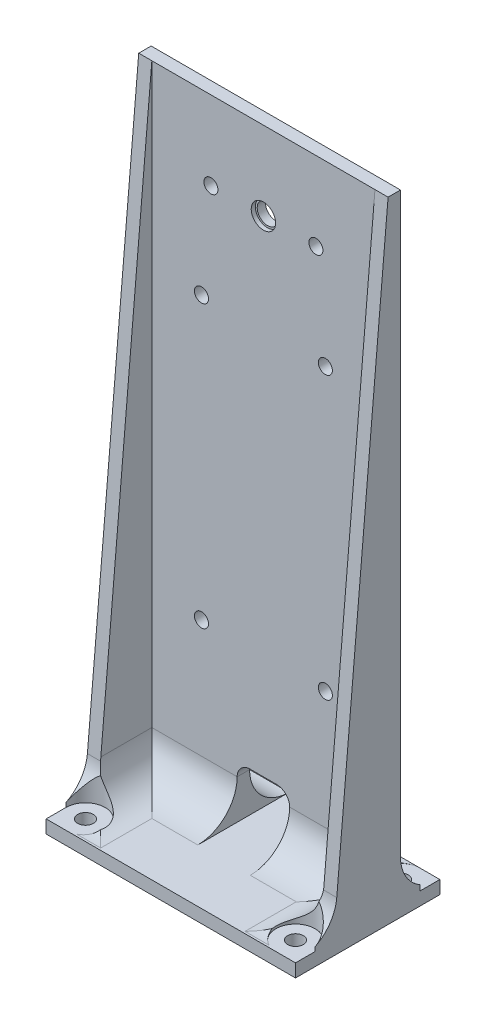
SolidWorks part; units mm, degrees
ref_plane "Front Plane" through (0, 0, 0) normal (0, 0, 1) x (1, 0, 0)
ref_plane "Top Plane" through (0, 0, 0) normal (0, 1, 0) x (1, 0, 0)
ref_plane "Right Plane" through (0, 0, 0) normal (1, 0, 0) x (0, 0, -1)
sketch "Sketch1" plane through (0, 0, 0) normal (0, 1, 0) x (1, 0, 0)
  line L0 (-30.1625, 17.4625) -> (30.1625, 17.4625)
  line L1 (-25.4, -12.7) -> (25.4, -12.7)
  line L2 (-25.4, -12.7) -> (-25.4, 12.7)
  line L3 (-25.4, 12.7) -> (25.4, 12.7)
  line L4 (25.4, -12.7) -> (25.4, 12.7)
  line L5 (-25.4, -12.7) -> (25.4, 12.7) construction
  line L6 (-25.4, 12.7) -> (25.4, -12.7) construction
  line L7 (30.1625, -17.4625) -> (30.1625, 17.4625)
  line L8 (-30.1625, -17.4625) -> (30.1625, -17.4625)
  line L9 (-30.1625, -17.4625) -> (-30.1625, 17.4625)
  point P0 (0, 0)
  dimension "D1" = 50.8
  dimension "D2" = 25.4
  dimension "D3" = 4.7625
extrude "Boss-Extrude1" add sketch "Sketch1" along normal blind 3.175 contours L1 L4 L3 L2 | L9 L8 L7 L0 L4 L1 L2 L3 region at (0, 0, -16.7654) region at (0, 0, 0)
hole_wizard "#6 Clearance Hole1" positions "Sketch2" profile "Sketch3" hole size "#6" standard "ANSI Inch"
sketch "Sketch2" plane through (0, 0, 0) normal (0, -1, 0) x (-1, 0, 0)
  point P0 (25.4, -12.7)
  point P3 (25.4, 12.7)
  point P6 (-25.4, 12.7)
  point P9 (-25.4, -12.7)
sketch "Sketch3" plane through (-25.4, 0, 12.7) normal (1, 0, 0) x (0, 0, -1)
  line L0 (0, 0) -> (0, 7.4908)
  line L1 (0, 7.4908) -> (1.8986, 6.35)
  line L2 (1.8986, 6.35) -> (1.8986, 0)
  line L5 (1.8986, 0) -> (0, 0)
  line L10 (0, 7.4908) -> (-1.8987, 6.35) construction
  line L11 (0, -6.35) -> (0, 107.95) construction
  dimension "Hole Dia." = 3.7973
  dimension "Hole Depth" = 6.35
  dimension "Drill Angle" = 118
sketch "Sketch5" plane through (0, 3.175, 0) normal (0, 1, 0) x (1, 0, 0)
  line L0 (-30.1625, 17.4625) -> (30.1625, 17.4625) construction
  line L1 (-30.1625, -17.4625) -> (30.1625, -17.4625) construction
  line L2 (-30.1625, -17.4625) -> (-30.1625, 17.4625)
  line L3 (-30.1625, 17.4625) -> (30.1625, 17.4625) construction
  line L4 (30.1625, -17.4625) -> (30.1625, 17.4625)
  line L5 (-30.1625, -17.4625) -> (30.1625, 17.4625) construction
  line L6 (-30.1625, 17.4625) -> (30.1625, -17.4625) construction
  line L7 (30.1625, -17.4625) -> (30.1625, 17.4625) construction
  line L8 (30.1625, -7.9375) -> (-30.1625, -7.9375)
  line L9 (30.1625, -7.9375) -> (30.1625, 7.9375)
  line L10 (30.1625, 7.9375) -> (-30.1625, 7.9375)
  line L11 (-30.1625, -7.9375) -> (-30.1625, 7.9375)
  line L12 (30.1625, -7.9375) -> (-30.1625, 7.9375) construction
  line L13 (30.1625, 7.9375) -> (-30.1625, -7.9375) construction
  circle A1 centre (25.4, 12.7) radius 1.8986 construction
  point P0 (0, 0)
  point P12 (0, 0)
  dimension "D1" = 4.7625
extrude "Boss-Extrude2" add sketch "Sketch5" along normal blind 149.225 contours L4 L10 L2 L8 region at (0, 3.175, 0)
sketch "Sketch10" plane through (-30.1625, 0, 0) normal (-1, 0, 0) x (0, 0, 1)
  line L0 (7.9375, 152.4) -> (-7.9375, 152.4) construction
  line L1 (-4.9375, 152.4) -> (7.9375, 152.4)
  line L2 (-4.9375, 152.4) -> (-4.9375, 3.175)
  line L3 (-4.9375, 3.175) -> (7.9375, 3.175)
  line L4 (7.9375, 152.4) -> (7.9375, 3.175)
  line L5 (7.9375, 3.175) -> (17.4625, 3.175) construction
  line L6 (-7.9375, 152.4) -> (-7.9375, 3.175) construction
  line L7 (7.9375, 152.4) -> (7.9375, 3.175) construction
  dimension "D1" = 3
  dimension "D2" = 0
extrude "Cut-Extrude4" cut sketch "Sketch10" against normal through all
sketch "Sketch11" plane through (0, 0, -4.9375) normal (0, 0, 1) x (1, 0, 0)
  line L1 (30.1625, 152.4) -> (-30.1625, 152.4) construction
  line L3 (-30.1625, 0) -> (30.1625, 0) construction
  circle A0 centre (0, 133.35) radius 2.95
  point P2 (0, 0)
  point P6 (0, 105.5126)
  point P9 (0, 152.4)
  dimension "D1" = 5.9
  dimension "D2" = 133.35
extrude "Cut-Extrude5" cut sketch "Sketch11" against normal offset from surface 2 and the other way through all up to face at (0, 77.7875, -7.9375)
sketch "Sketch12" plane through (0, 0, -5.9375) normal (0, 0, 1) x (1, 0, 0)
  circle A0 centre (0, 133.35) radius 2.5
  dimension "D1" = 5
extrude "Cut-Extrude6" cut sketch "Sketch12" against normal blind 2
sketch "Sketch17" plane through (0, 0, -7.9375) normal (0, 0, -1) x (-1, 0, 0)
  line L0 (-12.7, 133.35) -> (12.7, 133.35) construction
  circle A1 centre (0, 133.35) radius 2.5 construction
  circle A2 centre (0, 133.35) radius 2.5
  point P5 (0, 133.35)
  dimension "D1" = 25.4
hole_wizard "M3 Clearance Hole1" positions "Sketch18" profile "Sketch20" hole size "M3" standard "ANSI Metric" end condition through all
sketch "Sketch18" plane through (0, 0, -7.9375) normal (0, 0, -1) x (-1, 0, 0)
  point P0 (-12.7, 133.35)
  point P3 (12.7, 133.35)
sketch "Sketch20" plane through (12.7, 133.35, -7.9375) normal (1, 0, 0) x (0, 1, 0)
  line L0 (0, 0) -> (0, 25.4)
  line L1 (0, 25.4) -> (1.7, 25.4)
  line L2 (1.7, 25.4) -> (1.7, 0)
  line L5 (1.7, 0) -> (0, 0)
  line L11 (0, -6.35) -> (0, 107.95) construction
  dimension "Thru Hole Dia." = 3.4
  dimension "Thru Hole Depth" = 25.4
sketch "Sketch24" plane through (0, 0, -4.9375) normal (0, 0, 1) x (1, 0, 0)
  line L0 (30.1625, 3.175) -> (-30.1625, 3.175) construction
  line L1 (-14.986, 109.347) -> (14.986, 109.347)
  line L2 (-14.986, 109.347) -> (-14.986, 41.275)
  line L3 (-14.986, 41.275) -> (14.986, 41.275)
  line L4 (14.986, 109.347) -> (14.986, 41.275)
  point P4 (0, 41.275)
  point P6 (15.7587, 113.9496)
  dimension "D1" = 29.972
  dimension "D2" = 68.072
  dimension "D3" = 38.1
hole_wizard "M3 Clearance Hole2" positions "Sketch25" profile "Sketch26" hole size "M3" standard "ANSI Metric" end condition through all
sketch "Sketch25" plane through (0, 0, -4.9375) normal (0, 0, 1) x (1, 0, 0)
  point P0 (-14.986, 109.347)
  point P3 (14.986, 109.347)
  point P6 (14.986, 41.275)
  point P9 (-14.986, 41.275)
sketch "Sketch26" plane through (-14.986, 109.347, -4.9375) normal (1, 0, 0) x (0, -1, 0)
  line L0 (0, 0) -> (0, 12.525)
  line L1 (0, 12.525) -> (1.7, 12.525)
  line L2 (1.7, 12.525) -> (1.7, 0)
  line L5 (1.7, 0) -> (0, 0)
  line L11 (0, -6.35) -> (0, 107.95) construction
  dimension "Thru Hole Dia." = 3.4
  dimension "Thru Hole Depth" = 12.525
sketch "Sketch27" plane through (-30.1625, 0, 0) normal (-1, 0, 0) x (0, 0, 1)
  line L0 (17.4625, 3.175) -> (-4.9375, 3.175) construction
  line L1 (-4.9375, 152.4) -> (-4.9375, 3.175) construction
  line L2 (17.4625, 3.175) -> (-4.9375, 3.175)
  line L3 (-4.9375, 152.4) -> (-4.9375, 3.175)
  line L4 (-4.9375, 152.4) -> (8.2487, 3.175)
  line M1 (-4.9375, 3.175) -> (-4.9375, 152.4)
  dimension "D1" = 6.35
extrude "Boss-Extrude5" add sketch "Sketch27" against normal blind 3.175 contours L4 L2 M1 region at (-30.1625, 52.9167, -0.5421)
mirror "Mirror1" about plane through (0, 0, 0) normal (1, 0, 0) of "Boss-Extrude5"
sketch "Sketch28" plane through (0, 0, -4.9375) normal (0, 0, 1) x (1, 0, 0)
  line L0 (26.9875, 3.175) -> (-26.9875, 3.175) construction
  line L1 (-6.35, 3.175) -> (6.35, 3.175)
  line L2 (-6.35, 3.175) -> (-6.35, 12.7)
  line L3 (-3.175, 15.875) -> (3.175, 15.875)
  line L4 (6.35, 3.175) -> (6.35, 12.7)
  line L5 (-6.35, 3.175) -> (6.35, 15.875) construction
  line L6 (-6.35, 15.875) -> (6.35, 3.175) construction
  arc A0 (3.175, 15.875) -> (6.35, 12.7) centre (3.175, 12.7) cw
  arc A1 (-6.35, 12.7) -> (-3.175, 15.875) centre (-3.175, 12.7) cw
  point P0 (0, 9.525)
  point P5 (0, 0)
  dimension "D3" = 3.175
  dimension "D1" = 12.7
  dimension "D2" = 12.7
extrude "Cut-Extrude7" cut sketch "Sketch28" against normal blind 3.175 contours L2 A1 L3 A0 L4 L1
fillet "Fillet4" radius 9.525 8 edges at (26.9875, 3.175, 1.6556) (28.575, 3.175, 8.2486) (16.6688, 3.175, -4.9375) (-16.6687, 3.175, -4.9375) (-26.9875, 3.175, 1.6556) (-28.575, 3.175, 8.2486) (-18.2563, 3.175, -7.9375) (18.2562, 3.175, -7.9375)
sketch "Sketch29" plane through (0, 3.175, 0) normal (0, 1, 0) x (1, 0, 0)
  line L4 (-30.1625, 17.4625) -> (-30.1625, -17.4625)
  line L5 (30.1625, 17.4625) -> (-30.1625, 17.4625)
  line L6 (30.1625, -17.4625) -> (30.1625, 17.4625)
  line L7 (-30.1625, -17.4625) -> (30.1625, -17.4625)
  line L8 (-30.1625, 17.4625) -> (-30.1625, -17.4625)
  line L9 (30.1625, 17.4625) -> (-30.1625, 17.4625)
  line L10 (30.1625, -17.4625) -> (30.1625, 17.4625)
  line L11 (-30.1625, -17.4625) -> (30.1625, -17.4625)
  circle A0 centre (-25.4, 12.7) radius 1.8986 construction
  circle A1 centre (-25.4, -12.7) radius 1.8986 construction
  circle A2 centre (25.4, -12.7) radius 1.8986 construction
  circle A3 centre (25.4, 12.7) radius 1.8986 construction
  circle A4 centre (-25.4, 12.7) radius 1.8986
  circle A5 centre (-25.4, -12.7) radius 1.8986
  circle A6 centre (25.4, -12.7) radius 1.8986
  circle A7 centre (25.4, 12.7) radius 1.8986
  arc A8 (25.4, 17.4625) -> (30.1625, 12.7) centre (25.4, 12.7) ccw
  arc A9 (30.1625, -12.7) -> (25.4, -17.4625) centre (25.4, -12.7) ccw
  arc A10 (-25.4, -17.4625) -> (-30.1625, -12.7) centre (-25.4, -12.7) ccw
  arc A11 (-30.1625, 12.7) -> (-25.4, 17.4625) centre (-25.4, 12.7) ccw
  line M3 (30.1625, -16.9691) -> (17.4625, -16.9691)
  line M11 (-17.4625, -16.9691) -> (-30.1625, -16.9691)
  dimension "D1" = 9.525
  dimension "D2" = 0
extrude "Cut-Extrude9" cut sketch "Sketch29" along normal through all contours L10 A9 A6 M3 | A10 L8 A5 M11 | L8 A11 L9 A4 | L9 A8 L10 A7 region at (-27.7813, 3.175, -17.3278) region at (-22.9565, 3.175, 8.7658) region at (27.7812, 3.175, -17.3278) region at (30.0312, 3.175, 14.8345)
